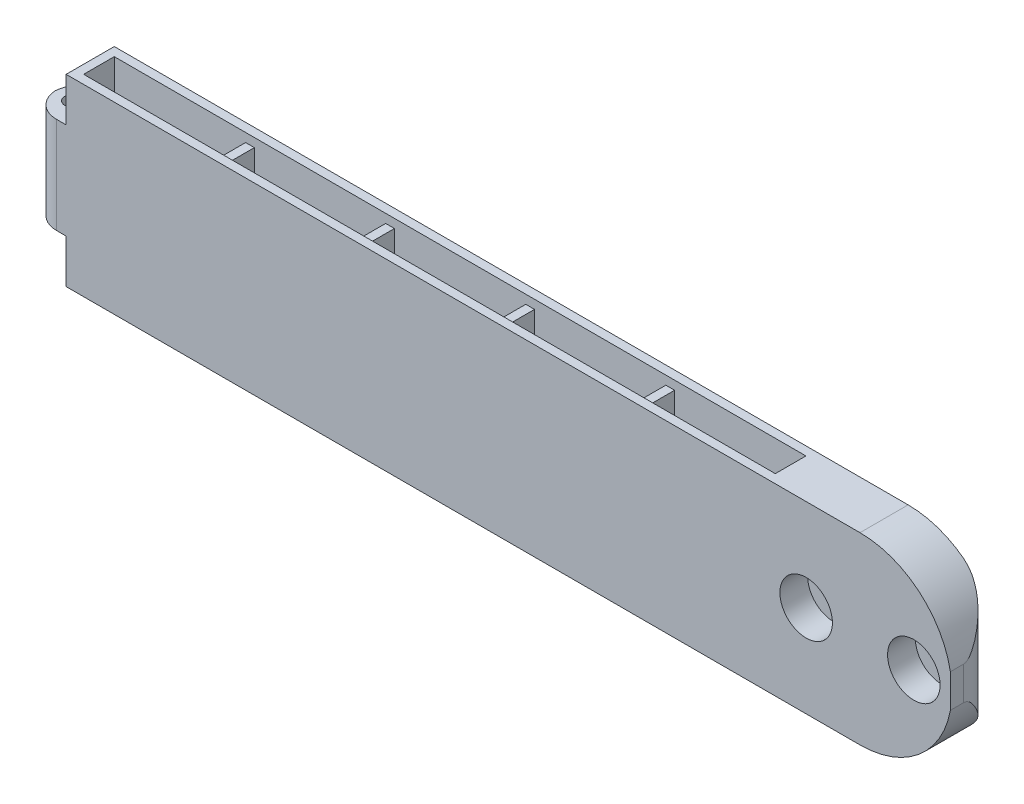
SolidWorks part; units mm, degrees
ref_plane "Front Plane" through (0, 0, 0) normal (0, 0, 1) x (1, 0, 0)
ref_plane "Top Plane" through (0, 0, 0) normal (0, 1, 0) x (1, 0, 0)
ref_plane "Right Plane" through (0, 0, 0) normal (1, 0, 0) x (0, 0, -1)
sketch "Sketch1" plane through (0, 0, 0) normal (0, 1, 0) x (1, 0, 0)
  line L1 (-52.5, -2.75) -> (52.5, -2.75)
  line L2 (-52.5, -2.75) -> (-52.5, 2.75)
  line L3 (-52.5, 2.75) -> (52.5, 2.75)
  line L4 (52.5, -2.75) -> (52.5, 2.75)
  line L5 (-52.5, -2.75) -> (52.5, 2.75) construction
  line L6 (-52.5, 2.75) -> (52.5, -2.75) construction
  point P0 (0, 0)
  dimension "D1" = 105
  dimension "D2" = 5.5
extrude "Boss-Extrude1" add sketch "Sketch1" along normal blind 21
sketch "Sketch2" plane through (0, 21, 0) normal (0, 1, 0) x (1, 0, 0)
  line L0 (-52.5, 2.75) -> (-52.5, -2.75) construction
  line L1 (31.5, 1.75) -> (16.5, 1.75)
  line L2 (31.5, 1.75) -> (31.5, -1.75)
  line L3 (31.5, -1.75) -> (16.5, -1.75)
  line L4 (16.5, 1.75) -> (16.5, -1.75)
  line L5 (31.5, 1.75) -> (16.5, -1.75) construction
  line L6 (31.5, -1.75) -> (16.5, 1.75) construction
  line L7 (0.5, 1.75) -> (15.5, 1.75)
  line L8 (0.5, 1.75) -> (0.5, -1.75)
  line L9 (0.5, -1.75) -> (15.5, -1.75)
  line L10 (15.5, 1.75) -> (15.5, -1.75)
  line L11 (0.5, 1.75) -> (15.5, -1.75) construction
  line L12 (0.5, -1.75) -> (15.5, 1.75) construction
  line L13 (-15.5, 1.75) -> (-0.5, 1.75)
  line L14 (-15.5, 1.75) -> (-15.5, -1.75)
  line L15 (-15.5, -1.75) -> (-0.5, -1.75)
  line L16 (-0.5, 1.75) -> (-0.5, -1.75)
  line L17 (-15.5, 1.75) -> (-0.5, -1.75) construction
  line L18 (-15.5, -1.75) -> (-0.5, 1.75) construction
  line L19 (-31.5, 1.75) -> (-16.5, 1.75)
  line L20 (-31.5, 1.75) -> (-31.5, -1.75)
  line L21 (-31.5, -1.75) -> (-16.5, -1.75)
  line L22 (-16.5, 1.75) -> (-16.5, -1.75)
  line L23 (-31.5, 1.75) -> (-16.5, -1.75) construction
  line L24 (-31.5, -1.75) -> (-16.5, 1.75) construction
  line L25 (-47.5, 1.75) -> (-32.5, 1.75)
  line L26 (-47.5, 1.75) -> (-47.5, -1.75)
  line L27 (-47.5, -1.75) -> (-32.5, -1.75)
  line L28 (-32.5, 1.75) -> (-32.5, -1.75)
  line L29 (-47.5, 1.75) -> (-32.5, -1.75) construction
  line L30 (-47.5, -1.75) -> (-32.5, 1.75) construction
  line L31 (52.5, 2.75) -> (-52.5, 2.75) construction
  line L32 (-52.5, -2.75) -> (52.5, -2.75) construction
  circle A0 centre (-50.5, 0) radius 0.9
  point P0 (24, 0)
  point P5 (8, 0)
  point P10 (-8, 0)
  point P15 (-24, 0)
  point P20 (-40, 0)
  dimension "D1" = 1.8
  dimension "D2" = 2
  dimension "D3" = 3
  dimension "D4" = 15
  dimension "D5" = 1
  dimension "D6" = 1
  dimension "D7" = 1
  dimension "D8" = 1
  dimension "D9" = 1
  dimension "D10" = 15
  dimension "D11" = 1
  dimension "D12" = 1
  dimension "D13" = 1
  dimension "D14" = 15
  dimension "D15" = 1
  dimension "D16" = 1
  dimension "D17" = 1
  dimension "D18" = 15
  dimension "D19" = 1
  dimension "D20" = 1
  dimension "D21" = 1
  dimension "D22" = 15
extrude "Cut-Extrude1" cut sketch "Sketch2" against normal blind 20
sketch "Sketch3" plane through (0, 0, 2.75) normal (0, 0, 1) x (1, 0, 0)
  line L1 (-48.5, 16) -> (-52.5, 16)
  line L2 (-48.5, 16) -> (-48.5, 21)
  line L3 (-48.5, 21) -> (-52.5, 21)
  line L4 (-52.5, 16) -> (-52.5, 21)
  line L5 (-48.5, 16) -> (-52.5, 21) construction
  line L6 (-48.5, 21) -> (-52.5, 16) construction
  line L7 (-48.5, 5) -> (-52.5, 5)
  line L8 (-48.5, 5) -> (-48.5, 0)
  line L9 (-48.5, 0) -> (-52.5, 0)
  line L10 (-52.5, 5) -> (-52.5, 0)
  line L11 (-48.5, 5) -> (-52.5, 0) construction
  line L12 (-48.5, 0) -> (-52.5, 5) construction
  point P0 (-50.5, 18.5)
  point P6 (-50.5, 2.5)
  dimension "D1" = 4
  dimension "D2" = 4
  dimension "D3" = 5
  dimension "D4" = 5
extrude "Cut-Extrude2" cut sketch "Sketch3" against normal blind 20
fillet "Fillet1" radius 2.9 2 edges at (-52.5, 10.5, 2.75) (-52.5, 10.5, -2.75)
fillet "Fillet2" radius 4 1 edges at (52.5, 10.5, -2.75)
sketch "Sketch4" plane through (0, 0, 2.75) normal (0, 0, 1) x (1, 0, 0)
  line L0 (52.5, 10.5) -> (-49.6, 10.5) construction
  line L1 (52.5, 21) -> (52.5, 0) construction
  line L2 (-49.6, 16) -> (-49.6, 5) construction
  circle A0 centre (48.325, 10.5) radius 3
  circle A1 centre (36.025, 10.5) radius 3
  dimension "D1" = 6
  dimension "D2" = 6
  dimension "D3" = 4.175
  dimension "D4" = 12.3
extrude "Cut-Extrude3" cut sketch "Sketch4" against normal blind 3.175
sketch "Sketch5" plane through (0, 21, 0) normal (0, 1, 0) x (1, 0, 0)
  line L1 (-16.5, 1.75) -> (-15.5, 1.75)
  line L2 (-16.5, 1.75) -> (-16.5, -1.75)
  line L3 (-16.5, -1.75) -> (-15.5, -1.75)
  line L4 (-15.5, 1.75) -> (-15.5, -1.75)
  line L5 (-32.5, 1.75) -> (-31.5, 1.75)
  line L6 (-32.5, 1.75) -> (-32.5, -1.75)
  line L7 (-32.5, -1.75) -> (-31.5, -1.75)
  line L8 (-31.5, -1.75) -> (-31.5, 1.75)
  line L13 (-0.5, 1.75) -> (0.5, 1.75)
  line L14 (-0.5, 1.75) -> (-0.5, -1.75)
  line L15 (-0.5, -1.75) -> (0.5, -1.75)
  line L16 (0.5, 1.75) -> (0.5, -1.75)
  line L17 (-0.5, 1.75) -> (0.5, -1.75) construction
  line L18 (-0.5, -1.75) -> (0.5, 1.75) construction
  line L19 (15.5, 1.75) -> (16.5, 1.75)
  line L20 (15.5, 1.75) -> (15.5, -1.75)
  line L21 (15.5, -1.75) -> (16.5, -1.75)
  line L22 (16.5, 1.75) -> (16.5, -1.75)
  point P10 (0, 0)
extrude "Cut-Extrude4" cut sketch "Sketch5" against normal blind 1
sketch "Sketch7" plane through (0, 0, 2.75) normal (0, 0, 1) x (1, 0, 0)
  line L0 (42.175, 21) -> (52.5, 21)
  line L2 (36.2722, 13.4898) -> (48.325, 13.5) construction
  line L3 (48.325, 13.5) -> (48.325, 10.5) construction
  line L4 (48.325, 10.5) -> (36.025, 10.5) construction
  line L5 (52.5, 21) -> (52.675, 10.5)
  line L6 (52.675, 10.5) -> (52.5, 0)
  line L7 (52.5, 0) -> (42.175, 0)
  circle A0 centre (36.025, 10.5) radius 3 construction
  circle A1 centre (48.325, 10.5) radius 3 construction
  circle A2 centre (42.175, 10.5) radius 10.5
  line M7 (-48.5, 0) -> (52.5, 0)
  line M8 (52.5, 0) -> (52.5, 21)
  line M9 (52.5, 21) -> (-48.5, 21)
extrude "Cut-Extrude5" cut sketch "Sketch7" against normal through all contours A2 M8 M9 | A2 M7 M8 region at (50.1641, 18.8215, 2.75) region at (50.1641, 2.1785, 2.75)
